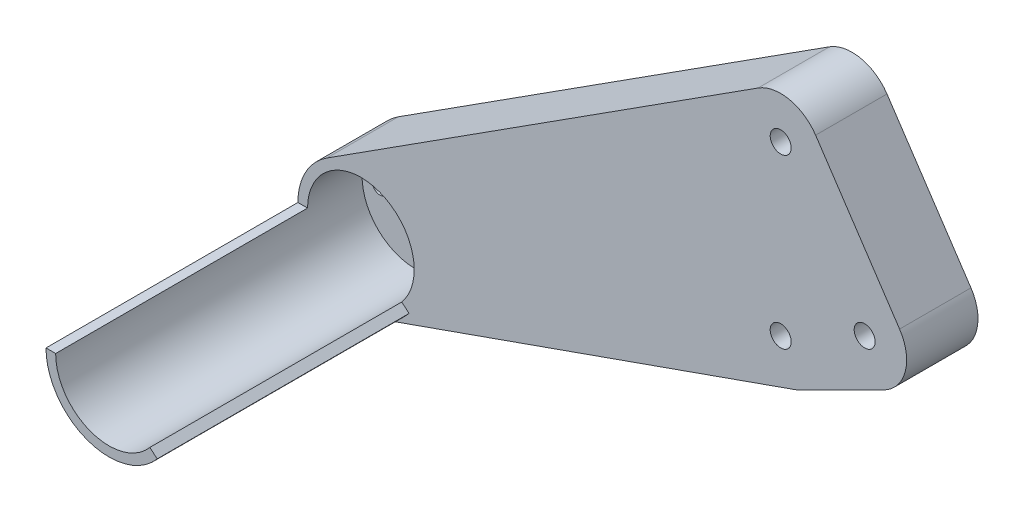
SolidWorks part; units mm, degrees
ref_plane "Front Plane" through (0, 0, 0) normal (0, 0, 1) x (1, 0, 0)
ref_plane "Top Plane" through (0, 0, 0) normal (0, 1, 0) x (1, 0, 0)
ref_plane "Right Plane" through (0, 0, 0) normal (1, 0, 0) x (0, 0, -1)
sketch "Sketch1" plane through (0, 0, 0) normal (0, 0, 1) x (1, 0, 0)
  line L1 (3.3289, -9.4297) -> (-95.0067, -44.1445)
  line L2 (-108.0914, -17.3695) -> (-5.3942, 48.4203)
  line L3 (8.3205, 45.547) -> (28.3205, 15.547)
  line L4 (24.4721, 1.0557) -> (4.4721, -8.9443)
  arc A0 (4.4721, -8.9443) -> (3.3289, -9.4297) centre (0, 0) cw
  arc A1 (-95.0067, -44.1445) -> (-108.0914, -17.3695) centre (-100, -30) cw
  arc A2 (-5.3942, 48.4203) -> (8.3205, 45.547) centre (0, 40) cw
  arc A3 (28.3205, 15.547) -> (24.4721, 1.0557) centre (20, 10) cw
  dimension "D1" = 15
  dimension "D5" = 10
  dimension "D8" = 10
  dimension "D9" = 10
  dimension "D2" = 30
  dimension "D3" = 40
  dimension "D4" = 100
  dimension "D6" = 20
  dimension "D7" = 30
extrude "Boss-Extrude1" add sketch "Sketch1" along normal blind 17
sketch "Sketch2" plane through (0, 0, 17) normal (0, 0, 1) x (1, 0, 0)
  circle A0 centre (-100, -30) radius 2.5
  circle A1 centre (0, 0) radius 2.5
  circle A2 centre (0, 40) radius 2.5
  circle A3 centre (20, 10) radius 2.5
  arc A4 (24.4721, 1.0557) -> (28.3205, 15.547) centre (20, 10) ccw construction
  dimension "D1" = 5
  dimension "D2" = 5
extrude "Cut-Extrude1" cut sketch "Sketch2" against normal through all
sketch "Sketch3" plane through (0, 0, 17) normal (0, 0, 1) x (1, 0, 0)
  line L0 (-108.5, -30) -> (-91.5, -30) construction
  circle A0 centre (-108.5, -30) radius 1.7
  circle A1 centre (-91.5, -30) radius 1.7
  circle A3 centre (-100, -30) radius 2.5 construction
  point P4 (-100, -30)
  dimension "D1" = 3.4
  dimension "D2" = 17
extrude "Cut-Extrude2" cut sketch "Sketch3" against normal through all
sketch "Sketch7" plane through (0, 0, 0) normal (0, 0, -1) x (-1, 0, 0)
  circle A0 centre (100, -30) radius 12.7
  dimension "D1" = 25.4
extrude "Cut-Extrude6" [suppressed] cut sketch "Sketch7" against normal blind 13
sketch "Sketch6" plane through (0, 0, 17) normal (0, 0, 1) x (1, 0, 0)
  circle A0 centre (-100, -30) radius 12.7
  dimension "D1" = 25.4
extrude "Cut-Extrude5" cut sketch "Sketch6" against normal blind 13
sketch "Sketch4" [suppressed] plane through (0, 0, 13) normal (0, 0, -1) x (-1, 0, 0)
  circle A0 centre (100, -30) radius 5.5
  dimension "D1" = 11
extrude "Cut-Extrude3" [suppressed] cut sketch "Sketch4" against normal blind 0.9
sketch "Sketch5" plane through (0, 0, 4) normal (0, 0, 1) x (1, 0, 0)
  circle A0 centre (-100, -30) radius 5.5
  dimension "D1" = 11
extrude "Cut-Extrude4" cut sketch "Sketch5" against normal blind 0.9
sketch "Sketch8" [suppressed] plane through (0, 0, 0) normal (0, 0, -1) x (-1, 0, 0)
  line L0 (112.7, -30) -> (115, -30)
  line L2 (87.0096, -37.5) -> (89.0015, -36.35)
  line L4 (-8.3205, 45.547) -> (-28.3205, 15.547)
  line L5 (-24.4721, 1.0557) -> (-4.4721, -8.9443)
  line L6 (-3.3289, -9.4297) -> (95.0067, -44.1445)
  line L7 (108.0914, -17.3695) -> (5.3942, 48.4203)
  circle A0 centre (100, -30) radius 12.7 construction
  circle A1 centre (100, -30) radius 12.7 construction
  arc A2 (89.0015, -36.35) -> (112.7, -30) centre (100, -30) ccw
  arc A4 (5.3942, 48.4203) -> (-8.3205, 45.547) centre (0, 40) ccw
  arc A5 (-28.3205, 15.547) -> (-24.4721, 1.0557) centre (-20, 10) ccw
  arc A6 (-4.4721, -8.9443) -> (-3.3289, -9.4297) centre (0, 0) ccw
  arc A7 (95.0067, -44.1445) -> (108.0914, -17.3695) centre (100, -30) ccw
  arc A11 (87.0096, -37.5) -> (115, -30) centre (100, -30) ccw
  dimension "D2" = 150
  dimension "D1" = 0
extrude "Boss-Extrude2" [suppressed] add sketch "Sketch8" along normal blind 60
sketch "Sketch9" plane through (0, 0, 17) normal (0, 0, 1) x (1, 0, 0)
  line L0 (-90.2712, -38.1634) -> (-88.5093, -39.6418)
  line L1 (-112.7, -30) -> (-115, -30)
  circle A0 centre (-100, -30) radius 12.7 construction
  arc A1 (-112.7, -30) -> (-90.2712, -38.1634) centre (-100, -30) ccw
  arc A3 (-115, -30) -> (-88.5093, -39.6418) centre (-100, -30) ccw
  dimension "D1" = 15
  dimension "D2" = 140
extrude "Boss-Extrude3" add sketch "Sketch9" along normal blind 60
